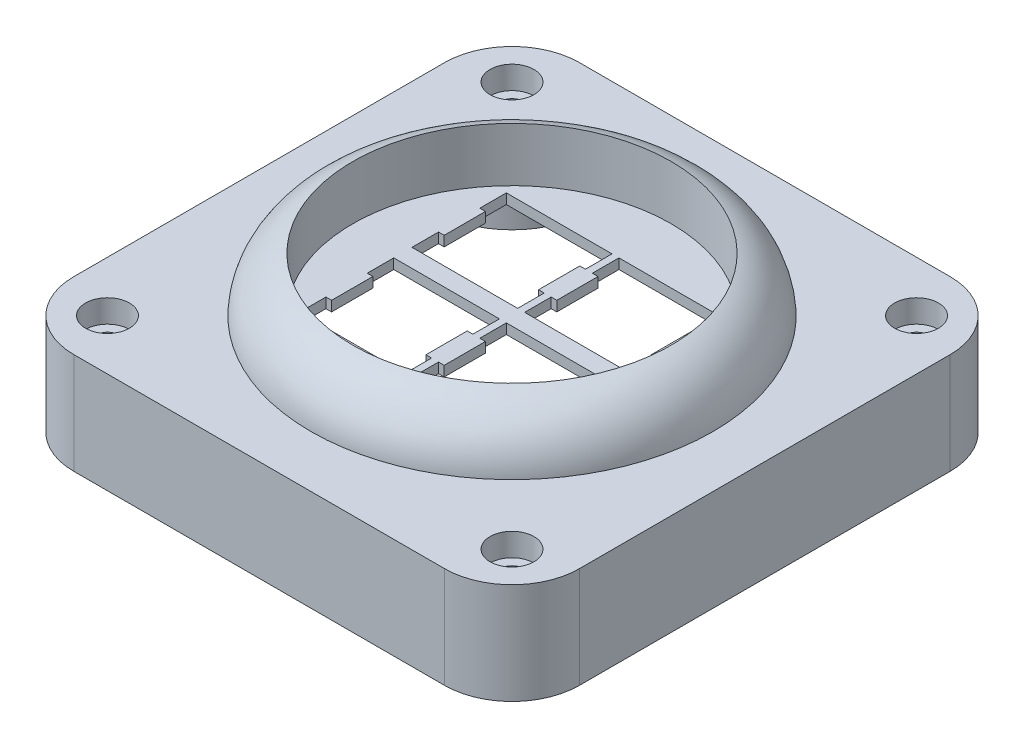
SolidWorks part; units mm, degrees
note: The reader was unsure of these and kept them because the rebuilt part matched: shared geometry of "Skizze1<3>".
ref_plane "Ebene vorne" through (0, 0, 0) normal (0, 0, 1) x (1, 0, 0)
ref_plane "Ebene oben" through (0, 0, 0) normal (0, 1, 0) x (1, 0, 0)
ref_plane "Ebene rechts" through (0, 0, 0) normal (1, 0, 0) x (0, 0, -1)
sketch "Skizze1" plane through (0, 0, 0) normal (0, 1, 0) x (1, 0, 0)
  line L0 (-22.5, 34.5) -> (22.5, 34.5)
  line L1 (-37.5, -37.5) -> (37.5, -37.5)
  line L2 (-37.5, -37.5) -> (-37.5, 22.5)
  line L3 (-37.5, 37.5) -> (37.5, 37.5)
  line L4 (37.5, -37.5) -> (37.5, 37.5)
  line L5 (-37.5, -37.5) -> (37.5, 37.5) construction
  line L6 (-37.5, 37.5) -> (37.5, -37.5) construction
  line L7 (-37.5, 37.5) -> (-35, 37.5)
  line L8 (-37.5, 37.5) -> (-37.5, 22.5)
  line L9 (-34.5, 22.5) -> (-22.5, 22.5)
  line L10 (-22.5, 34.5) -> (-22.5, 22.5)
  line L11 (34.5, -22.5) -> (34.5, 22.5)
  line L12 (-22.5, -34.5) -> (22.5, -34.5)
  line L13 (-34.5, -22.5) -> (-34.5, 22.5)
  line L14 (-34.5, 34.5) -> (34.5, 34.5) construction
  line L15 (-34.5, -34.5) -> (-34.5, 34.5) construction
  line L16 (-37.5, -37.5) -> (-37.5, 37.5) construction
  line L17 (-37.5, 37.5) -> (37.5, 37.5) construction
  line L18 (0, -37.5) -> (0, 37.5) construction
  line L19 (-37.5, 0) -> (37.5, 0) construction
  line L20 (34.5, 22.5) -> (22.5, 22.5)
  line L21 (22.5, 34.5) -> (22.5, 22.5)
  line L22 (22.5, -34.5) -> (22.5, -22.5)
  line L23 (34.5, -22.5) -> (22.5, -22.5)
  line L24 (-22.5, -34.5) -> (-22.5, -22.5)
  line L25 (-34.5, -22.5) -> (-22.5, -22.5)
  line L26 (34.5, -34.5) -> (34.5, 34.5) construction
  line L27 (-34.5, -34.5) -> (34.5, -34.5) construction
  line L28 (-37.5, -34.5) -> (-22.5, -34.5) construction
  line L29 (1.3529, 5.2899) -> (0.5147, 5.2899)
  line L30 (1.3529, 1.3529) -> (15.3483, 1.3529)
  line L31 (1.3529, 5.2899) -> (1.3529, 11.4113)
  line L32 (1.3529, 15.3483) -> (15.3483, 15.3483)
  line L33 (15.3483, 5.2899) -> (15.3483, 11.4113)
  line L34 (1.3529, 1.3529) -> (15.3483, 15.3483) construction
  line L35 (1.3529, 15.3483) -> (15.3483, 1.3529) construction
  line L36 (15.3483, 1.3529) -> (16.1865, 1.3529)
  line L37 (15.3483, 5.2899) -> (16.1865, 5.2899)
  line L38 (16.1865, 1.3529) -> (16.1865, 5.2899)
  line L39 (0.5147, 1.3529) -> (0.5147, 5.2899)
  line L40 (1.3529, 11.4113) -> (0.5147, 11.4113)
  line L41 (0.5147, 15.3483) -> (0.5147, 11.4113)
  line L42 (15.3483, 11.4113) -> (16.1865, 11.4113)
  line L43 (16.1865, 15.3483) -> (16.1865, 11.4113)
  line L44 (16.1865, 15.3483) -> (15.3483, 15.3483)
  line L45 (1.3529, 1.3529) -> (0.5147, 1.3529)
  line L46 (1.3529, 15.3483) -> (0.5147, 15.3483)
  line L47 (-1.3529, 15.3483) -> (-15.3483, 1.3529) construction
  line L48 (-1.3529, 1.3529) -> (-15.3483, 15.3483) construction
  line L49 (-1.3529, 15.3483) -> (-0.5147, 15.3483)
  line L50 (-1.3529, 1.3529) -> (-0.5147, 1.3529)
  line L51 (-16.1865, 15.3483) -> (-15.3483, 15.3483)
  line L52 (-16.1865, 15.3483) -> (-16.1865, 11.4113)
  line L53 (-15.3483, 11.4113) -> (-16.1865, 11.4113)
  line L54 (-0.5147, 15.3483) -> (-0.5147, 11.4113)
  line L55 (-1.3529, 11.4113) -> (-0.5147, 11.4113)
  line L56 (-0.5147, 1.3529) -> (-0.5147, 5.2899)
  line L57 (-16.1865, 1.3529) -> (-16.1865, 5.2899)
  line L58 (-15.3483, 5.2899) -> (-16.1865, 5.2899)
  line L59 (-15.3483, 1.3529) -> (-16.1865, 1.3529)
  line L60 (-15.3483, 5.2899) -> (-15.3483, 11.4113)
  line L61 (-1.3529, 15.3483) -> (-15.3483, 15.3483)
  line L62 (-1.3529, 5.2899) -> (-1.3529, 11.4113)
  line L63 (-1.3529, 1.3529) -> (-15.3483, 1.3529)
  line L64 (-1.3529, 5.2899) -> (-0.5147, 5.2899)
  line L65 (-1.3529, -1.3529) -> (-15.3483, -15.3483) construction
  line L66 (-1.3529, -15.3483) -> (-15.3483, -1.3529) construction
  line L67 (1.3529, -15.3483) -> (15.3483, -1.3529) construction
  line L68 (1.3529, -1.3529) -> (15.3483, -15.3483) construction
  line L69 (-1.3529, -5.2899) -> (-0.5147, -5.2899)
  line L70 (-1.3529, -1.3529) -> (-15.3483, -1.3529)
  line L71 (-1.3529, -5.2899) -> (-1.3529, -11.4113)
  line L72 (-1.3529, -15.3483) -> (-15.3483, -15.3483)
  line L73 (-15.3483, -5.2899) -> (-15.3483, -11.4113)
  line L74 (-15.3483, -1.3529) -> (-16.1865, -1.3529)
  line L75 (-15.3483, -5.2899) -> (-16.1865, -5.2899)
  line L76 (-16.1865, -1.3529) -> (-16.1865, -5.2899)
  line L77 (-0.5147, -1.3529) -> (-0.5147, -5.2899)
  line L78 (-1.3529, -11.4113) -> (-0.5147, -11.4113)
  line L79 (-0.5147, -15.3483) -> (-0.5147, -11.4113)
  line L80 (-15.3483, -11.4113) -> (-16.1865, -11.4113)
  line L81 (-16.1865, -15.3483) -> (-16.1865, -11.4113)
  line L82 (-16.1865, -15.3483) -> (-15.3483, -15.3483)
  line L83 (-1.3529, -1.3529) -> (-0.5147, -1.3529)
  line L84 (-1.3529, -15.3483) -> (-0.5147, -15.3483)
  line L85 (1.3529, -15.3483) -> (0.5147, -15.3483)
  line L86 (1.3529, -1.3529) -> (0.5147, -1.3529)
  line L87 (16.1865, -15.3483) -> (15.3483, -15.3483)
  line L88 (16.1865, -15.3483) -> (16.1865, -11.4113)
  line L89 (15.3483, -11.4113) -> (16.1865, -11.4113)
  line L90 (0.5147, -15.3483) -> (0.5147, -11.4113)
  line L91 (1.3529, -11.4113) -> (0.5147, -11.4113)
  line L92 (0.5147, -1.3529) -> (0.5147, -5.2899)
  line L93 (16.1865, -1.3529) -> (16.1865, -5.2899)
  line L94 (15.3483, -5.2899) -> (16.1865, -5.2899)
  line L95 (15.3483, -1.3529) -> (16.1865, -1.3529)
  line L96 (15.3483, -5.2899) -> (15.3483, -11.4113)
  line L97 (1.3529, -15.3483) -> (15.3483, -15.3483)
  line L98 (1.3529, -5.2899) -> (1.3529, -11.4113)
  line L99 (1.3529, -1.3529) -> (15.3483, -1.3529)
  line L100 (1.3529, -5.2899) -> (0.5147, -5.2899)
  circle A0 centre (-30, -30) radius 1.6
  circle A1 centre (30, 30) radius 1.6
  circle A2 centre (-30, 30) radius 1.6
  circle A3 centre (30, -30) radius 1.6
  point P0 (8.3506, 8.3506)
  point P9 (-41.5533, 41.5533)
  point P31 (8.3506, 8.3506)
  point P32 (8.3506, 8.3506)
  point P56 (-31.6951, 28.8887)
  point P57 (-30, 30)
  point P74 (-8.3506, 8.3506)
  point P107 (-8.3506, -8.3506)
  point P108 (8.3506, -8.3506)
  dimension "D4" = 3
  dimension "D5" = 13.9954
  dimension "D8" = 16.7012
  dimension "D1" = 75
  dimension "D2" = 75
  dimension "D3" = 15
  dimension "D6" = 0.8382
  dimension "D7" = 3.937
  dimension "D9" = 16.7012
extrude "Aufsatz-Linear austragen1" add sketch "Skizze1" against normal blind 15
extrude "Aufsatz-Linear austragen2" add sketch "Skizze1<3>" against normal blind 1.5 contours L13 L25 L24 L12 L22 L23 L11 L20 L21 L0 L10 L9
sketch "Skizze1<3>" plane through (0, 0, 0) normal (0, 1, 0) x (1, 0, 0) same geometry as "Skizze1"
fillet "Verrundung1" radius 10 4 edges at (37.5, -7.5, 37.5) (37.5, -7.5, -37.5) (-37.5, -7.5, -37.5) (-37.5, -7.5, 37.5)
fillet "Verrundung2" radius 12 4 edges at (22.5, -8.25, 22.5) (-22.5, -8.25, 22.5) (22.5, -8.25, -22.5) (-22.5, -8.25, -22.5)
sketch "Skizze3" plane through (0, 0, 0) normal (1, 0, 0) x (0, 0, -1)
  line L0 (23.6089, 0) -> (29.8037, 0)
  line L1 (23.6089, 0) -> (23.6089, 8)
  line L4 (0, 0) -> (0, 8.2563) construction
  line L5 (37.5, 0) -> (27.5, 0) construction
  arc A0 (29.8037, 0) -> (23.6089, 8) centre (20.8188, -0.559) ccw
revolve "Rotation1" add sketch "Skizze3" angle 360 about L4
hole_wizard "Stirnsenkung für M3 Flachkopfschraube mit Schlitz1" [suppressed] positions "Skizze7" profile "Skizze6" counterbore size "M3" standard "DIN"
sketch "Skizze7" plane through (0, 0, 0) normal (0, 1, 0) x (1, 0, 0)
  circle A0 centre (-30, 30) radius 1.5 construction
  point P0 (-29.1323, 31.2236)
  point P4 (30, 30)
sketch "Skizze6" plane through (-29.1323, 0, -31.2236) normal (1, 0, 0) x (0, 0, 1)
  line L0 (0, 0) -> (0, 30)
  line L1 (0, 30) -> (1.8, 30)
  line L3 (1.8, 30) -> (1.8, 2.4)
  line L4 (1.8, 2.4) -> (3.5, 2.4)
  line L5 (3.5, 2.4) -> (3.5, 0)
  line L7 (3.5, 0) -> (0, 0)
  line L11 (0, -6.35) -> (0, 107.95) construction
  dimension "Bohrerdurchmesser" = 3.6
  dimension "Bohrungstiefe" = 30
  dimension "Senkdurchmesser2" = 7
  dimension "Senktiefe2" = 2.4
hole_wizard "Stirnsenkung für M3 Zylinderschraube mit Innensechskant1" positions "Skizze9" profile "Skizze8" counterbore size "M3" standard "DIN" end condition through all
sketch "Skizze9" plane through (0, 0, 0) normal (0, 1, 0) x (1, 0, 0)
  point P0 (-30, 30)
  point P3 (30, 30)
  point P6 (-30, -30)
  point P9 (30, -30)
sketch "Skizze8" plane through (-30, 0, -30) normal (1, 0, 0) x (0, 0, 1)
  line L0 (0, 0) -> (0, 15)
  line L1 (0, 15) -> (1.8, 15)
  line L3 (1.8, 15) -> (1.8, 3.4)
  line L4 (1.8, 3.4) -> (3.25, 3.4)
  line L5 (3.25, 3.4) -> (3.25, 0)
  line L7 (3.25, 0) -> (0, 0)
  line L11 (0, -6.35) -> (0, 107.95) construction
  dimension "Bohrerdurchmesser" = 3.6
  dimension "Bohrungstiefe" = 15
  dimension "Senkdurchmesser2" = 6.5
  dimension "Senktiefe2" = 3.4
